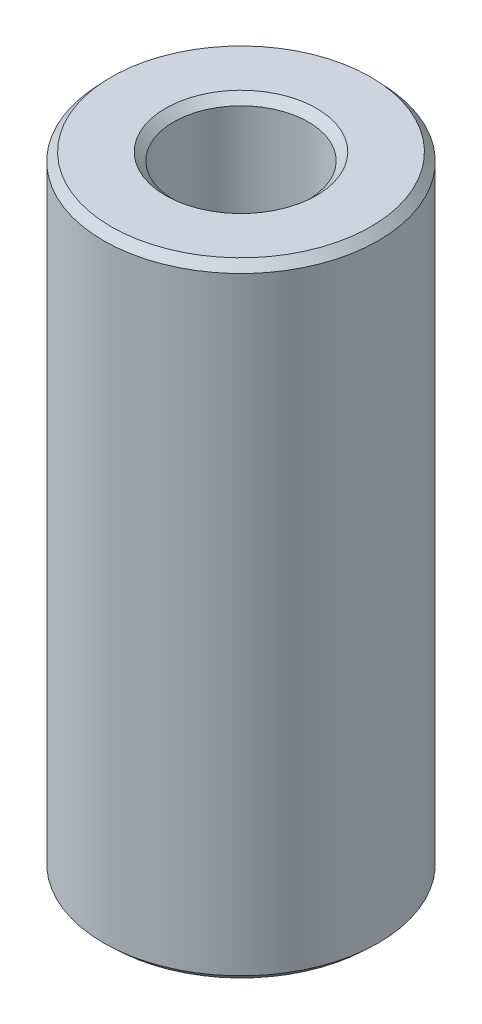
SolidWorks part; units mm, degrees
ref_plane "Front Plane" through (0, 0, 0) normal (0, 0, 1) x (1, 0, 0)
ref_plane "Top Plane" through (0, 0, 0) normal (0, 1, 0) x (1, 0, 0)
ref_plane "Right Plane" through (0, 0, 0) normal (1, 0, 0) x (0, 0, -1)
sketch "Sketch1" plane through (0, 0, 0) normal (0, 1, 0) x (1, 0, 0)
  circle A0 centre (0, 0) radius 22.5
  dimension "SLEEVE_OD" = 45
extrude "Boss-Extrude1" add sketch "Sketch1" along normal blind 102.1987
sketch "Sketch2" plane through (0, 0, 0) normal (0, 1, 0) x (1, 0, 0)
  circle A0 centre (0, 0) radius 11.0263
  dimension "BORE_D" = 22.0526
extrude "Cut-Extrude1" cut sketch "Sketch2" along normal through all
chamfer "Chamfer1" distance 1.3442 angle 43.107 4 edges at (0, 102.1987, 11.0263) (0, 0, 11.0263) (0, 0, 22.5) (0, 102.1987, 22.5) first distance on face at (0, 102.1987, 11.0263) first distance on face at (0, 0, 11.0263) first distance on face at (0, 102.1987, 22.5)
